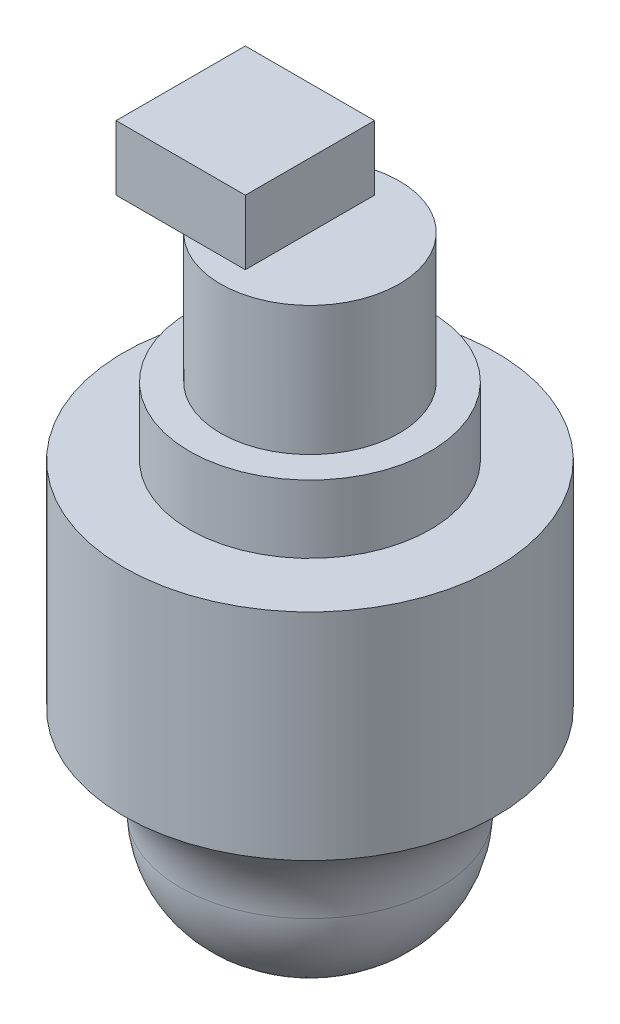
SolidWorks part; units mm, degrees
ref_plane "Front Plane" through (0, 0, 0) normal (0, 0, 1) x (1, 0, 0)
ref_plane "Top Plane" through (0, 0, 0) normal (0, 1, 0) x (1, 0, 0)
ref_plane "Right Plane" through (0, 0, 0) normal (1, 0, 0) x (0, 0, -1)
sketch "Sketch1" plane through (0, 0, 0) normal (0, 1, 0) x (1, 0, 0)
  circle A0 centre (0, 0) radius 21.971
  dimension "D1" = 43.942
extrude "Boss-Extrude1" add sketch "Sketch1" along normal blind 25.4
sketch "Sketch2" plane through (0, 25.4, 0) normal (0, 1, 0) x (1, 0, 0)
  circle A0 centre (0, 0) radius 14.224
  dimension "D1" = 28.448
extrude "Boss-Extrude2" add sketch "Sketch2" along normal blind 8.001
sketch "Sketch3" plane through (0, 33.401, 0) normal (0, 1, 0) x (1, 0, 0)
  circle A0 centre (0, 0) radius 10.541
  dimension "D1" = 21.082
extrude "Boss-Extrude3" add sketch "Sketch3" along normal blind 15.24
sketch "Sketch4" plane through (0, 48.641, 0) normal (0, 1, 0) x (1, 0, 0)
  line L1 (0, 0) -> (-15.24, 0)
  line L2 (0, 0) -> (0, 7.62)
  line L3 (0, 7.62) -> (-15.24, 7.62)
  line L4 (-15.24, 0) -> (-15.24, 7.62)
  line L5 (0, 0) -> (-15.24, 0)
  line L6 (0, 0) -> (0, -7.62)
  line L7 (0, -7.62) -> (-15.24, -7.62)
  line L8 (-15.24, 0) -> (-15.24, -7.62)
  dimension "D1" = 7.62
  dimension "D2" = 15.24
  dimension "D3" = 7.62
extrude "Boss-Extrude4" add sketch "Sketch4" along normal blind 7.62 contours L4 L3 L2 L6 L7 L8
sketch "Sketch5" plane through (0, 0, 0) normal (0, -1, 0) x (1, 0, 0)
  circle A0 centre (0, 0) radius 15.24
  dimension "D1" = 30.48
extrude "Boss-Extrude5" add sketch "Sketch5" along normal blind 22.86
fillet "Fillet1" radius 12.7 1 edges at (0, 0, 15.24)
fillet "Fillet2" radius 12.7 1 edges at (0, -22.86, -15.24)
